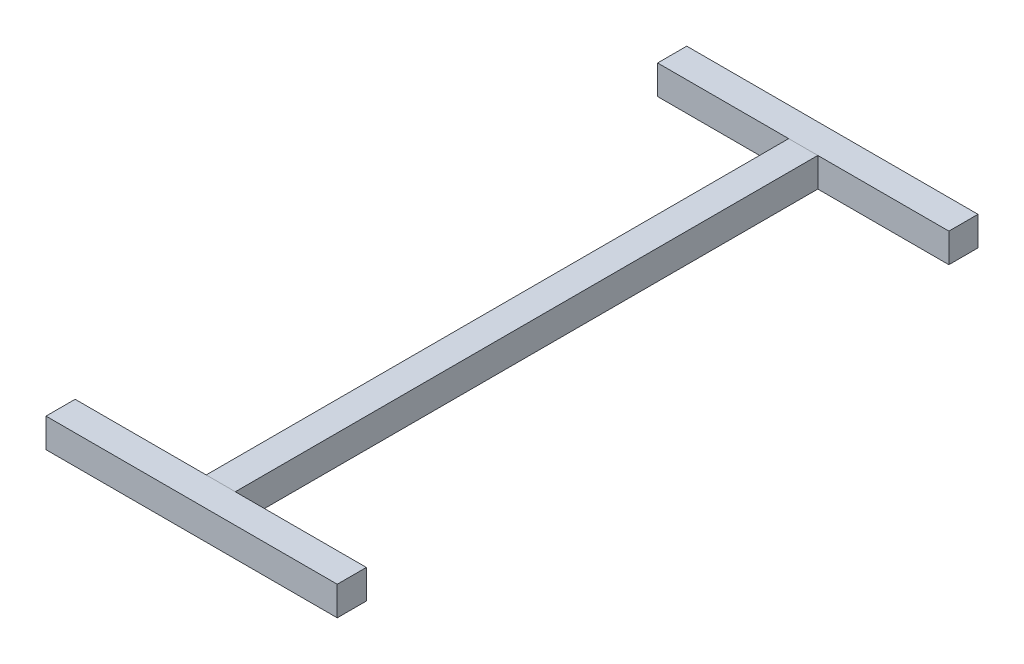
SolidWorks part; units mm, degrees
ref_plane "Спереди" through (0, 0, 0) normal (0, 0, 1) x (1, 0, 0)
ref_plane "Сверху" through (0, 0, 0) normal (0, 1, 0) x (1, 0, 0)
ref_plane "Справа" through (0, 0, 0) normal (1, 0, 0) x (0, 0, -1)
sketch "Эскиз1" plane through (0, 0, 0) normal (0, 0, 1) x (1, 0, 0)
  line L1 (10, -10) -> (-10, -10)
  line L2 (10, -10) -> (10, 10)
  line L3 (10, 10) -> (-10, 10)
  line L4 (-10, -10) -> (-10, 10)
  line L5 (10, -10) -> (-10, 10) construction
  line L6 (10, 10) -> (-10, -10) construction
  point P0 (0, 0)
  dimension "D1" = 20
  dimension "D2" = 20
extrude "Бобышка-Вытянуть1" add sketch "Эскиз1" along normal mid plane 400 contours L3 L4 L1 L2
sketch "Эскиз2" plane through (0, 0, 0) normal (1, 0, 0) x (0, 0, -1)
  line L0 (200, -10) -> (200, 10) construction
  line L1 (200, 10) -> (220, 10)
  line L2 (200, 10) -> (200, -10)
  line L3 (200, -10) -> (220, -10)
  line L4 (220, 10) -> (220, -10)
extrude "Бобышка-Вытянуть2" add sketch "Эскиз2" along normal mid plane 200 separate body
mirror "Зеркальное отражение1" about plane through (0, 0, 0) normal (0, 0, 1) of bodies 104
equation "\"W\"= 20мм'Размер профиля"
equation "\"D1@Эскиз1\"=\"W\""
equation "\"D2@Эскиз1\"=\"W\""
